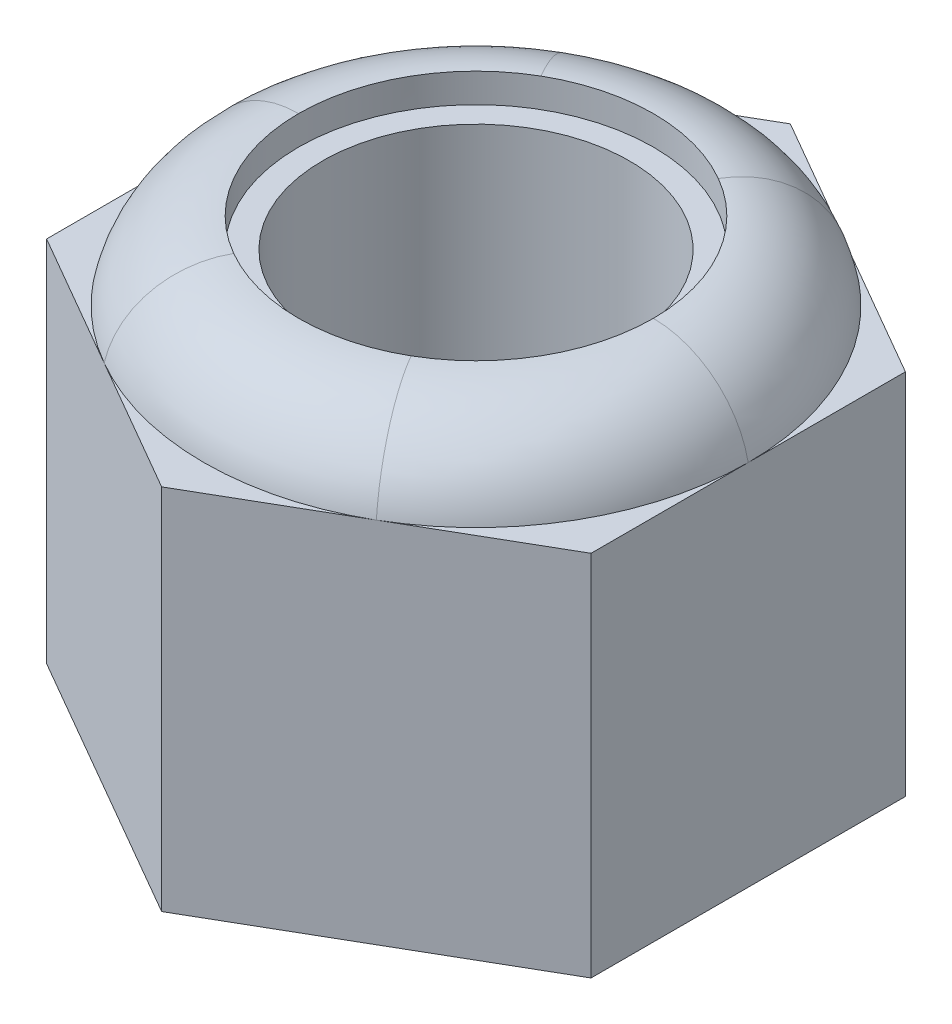
SolidWorks part; units mm, degrees
ref_plane "Front Plane" through (0, 0, 0) normal (0, 0, 1) x (1, 0, 0)
ref_plane "Top Plane" through (0, 0, 0) normal (0, 1, 0) x (1, 0, 0)
ref_plane "Right Plane" through (0, 0, 0) normal (1, 0, 0) x (0, 0, -1)
sketch "Sketch1" plane through (0, 0, 0) normal (0, 1, 0) x (1, 0, 0)
  line L10 (-7.1438, 4.1244) -> (-7.1438, 0)
  line L11 (-3.5719, 6.1867) -> (-7.1438, 4.1244)
  line L12 (7.1437, -4.1244) -> (7.1438, 0)
  line L13 (3.5719, -6.1867) -> (7.1437, -4.1244)
  line L14 (3.5719, -6.1867) -> (0, -8.2489)
  line L15 (0, -8.2489) -> (-7.1438, -4.1244)
  line L16 (-7.1438, -4.1244) -> (-7.1438, 0)
  line L17 (-3.5719, 6.1867) -> (0, 8.2489)
  line L18 (0, 8.2489) -> (7.1437, 4.1244)
  line L19 (7.1437, 4.1244) -> (7.1438, 0)
  circle A1 centre (0, 0) radius 4.0291
extrude "Boss-Extrude3" add sketch "Sketch1" along normal blind 9.652 separate body
sketch "Sketch3" plane through (0, 9.652, 0) normal (0, 1, 0) x (1, 0, 0)
  circle A0 centre (0, 0) radius 7.1438
  circle A1 centre (0, 0) radius 4.0291
extrude "Boss-Extrude4" add sketch "Sketch3" along normal blind 2.032
fillet "Fillet2" radius 2.54 1 edges at (0, 11.684, 7.1438)
sketch "Sketch4" plane through (0, 11.684, 0) normal (0, 1, 0) x (1, 0, 0)
  circle A0 centre (0, 0) radius 4.6551
extrude "Cut-Extrude1" cut sketch "Sketch4" against normal blind 0.762
